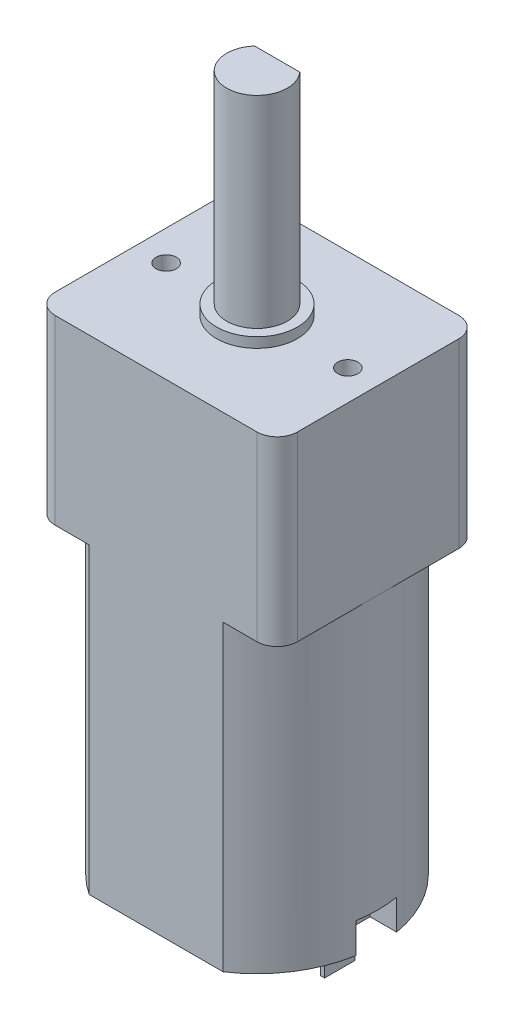
SolidWorks part; units mm, degrees
ref_plane "Front Plane" through (0, 0, 0) normal (0, 0, 1) x (1, 0, 0)
ref_plane "Top Plane" through (0, 0, 0) normal (0, 1, 0) x (1, 0, 0)
ref_plane "Right Plane" through (0, 0, 0) normal (1, 0, 0) x (0, 0, -1)
sketch "Sketch1" plane through (0, 0, 0) normal (0, 1, 0) x (1, 0, 0)
  line L0 (-3.3166, 5) -> (3.3166, 5)
  line L1 (-3.3166, -5) -> (3.3166, -5)
  arc A0 (-3.3166, 5) -> (-3.3166, -5) centre (0, 0) ccw
  arc A1 (3.3166, -5) -> (3.3166, 5) centre (0, 0) ccw
  dimension "D1" = 12
  dimension "D2" = 10
extrude "Boss-Extrude1" add sketch "Sketch1" along normal blind 15
sketch "Sketch2" plane through (0, 0, 0) normal (0, -1, 0) x (1, 0, 0)
  circle A0 centre (0, 0) radius 2.5
  dimension "D1" = 5
extrude "Boss-Extrude2" add sketch "Sketch2" along normal blind 1.2
sketch "Sketch3" plane through (0, 0, 0) normal (0, -1, 0) x (1, 0, 0)
  line L0 (0, 5) -> (0, -5) construction
  line L1 (-3.3166, 5) -> (3.3166, 5) construction
  line L2 (3.3166, -5) -> (-3.3166, -5) construction
  line L3 (4.1, -0.75) -> (3.9, -0.75)
  line L4 (-4.1, 0.75) -> (-3.9, 0.75)
  line L5 (-4.1, 0.75) -> (-4.1, -0.75)
  line L6 (-4.1, -0.75) -> (-3.9, -0.75)
  line L7 (-3.9, 0.75) -> (-3.9, -0.75)
  line L8 (3.9, 0.75) -> (3.9, -0.75)
  line L9 (4.1, 0.75) -> (3.9, 0.75)
  line L10 (4.1, 0.75) -> (4.1, -0.75)
  point P10 (-3.9, 0)
  point P15 (-4, -0.75)
  point P17 (4, -0.75)
  dimension "D1" = 1.5
  dimension "D2" = 0.2
  dimension "D3" = 8
extrude "Boss-Extrude3" add sketch "Sketch3" along normal blind 2
sketch "Sketch4" plane through (0, 0, 0) normal (0, -1, 0) x (1, 0, 0)
  line L0 (0, 5) -> (0, -5) construction
  line L1 (-6, 1) -> (-4.6, 1)
  line L2 (-6, 1) -> (-6, -1)
  line L3 (-6, -1) -> (-4.6, -1)
  line L4 (-4.6, 1) -> (-4.6, -1)
  line L5 (-3.3166, 5) -> (3.3166, 5) construction
  line L6 (3.3166, -5) -> (-3.3166, -5) construction
  line L7 (6, -1) -> (4.6, -1)
  line L8 (4.6, 1) -> (4.6, -1)
  line L9 (6, 1) -> (4.6, 1)
  line L10 (6, 1) -> (6, -1)
  arc A0 (-3.3166, 5) -> (-3.3166, -5) centre (0, 0) ccw construction
  point P13 (-6, 0)
  point P14 (-4.6, 0)
  dimension "D1" = 1.4
  dimension "D2" = 2
extrude "Cut-Extrude1" cut sketch "Sketch4" against normal blind 1.5
sketch "Sketch5" plane through (0, 15, 0) normal (0, 1, 0) x (1, 0, 0)
  line L0 (3.3166, 5) -> (-3.3166, 5) construction
  line L1 (-5, 5) -> (5, 5)
  line L2 (-6, 4) -> (-6, -4)
  line L3 (-5, -5) -> (5, -5)
  line L4 (6, 4) -> (6, -4)
  line L5 (-3.3166, -5) -> (3.3166, -5) construction
  arc A0 (3.3166, -5) -> (3.3166, 5) centre (0, 0) ccw construction
  arc A1 (-3.3166, 5) -> (-3.3166, -5) centre (0, 0) ccw construction
  arc A2 (5, 5) -> (6, 4) centre (5, 4) cw
  arc A3 (5, -5) -> (6, -4) centre (5, -4) ccw
  arc A4 (-6, -4) -> (-5, -5) centre (-5, -4) ccw
  arc A5 (-5, 5) -> (-6, 4) centre (-5, 4) ccw
  dimension "D1" = 1
extrude "Boss-Extrude4" add sketch "Sketch5" along normal blind 9
sketch "Sketch6" plane through (0, 24, 0) normal (0, 1, 0) x (1, 0, 0)
  line L0 (-1.118, 1) -> (1.118, 1)
  line L1 (-5, -5) -> (5, -5) construction
  arc A0 (-1.118, 1) -> (1.118, 1) centre (0, 0) ccw
  dimension "D1" = 3
  dimension "D2" = 1
extrude "Boss-Extrude5" add sketch "Sketch6" along normal blind 10.5
sketch "Sketch7" plane through (0, 24, 0) normal (0, 1, 0) x (1, 0, 0)
  circle A0 centre (0, 0) radius 2
  dimension "D1" = 4
extrude "Boss-Extrude6" add sketch "Sketch7" along normal blind 0.5
sketch "Sketch8" plane through (0, 24, 0) normal (0, 1, 0) x (1, 0, 0)
  line L0 (0, 5) -> (0, -5) construction
  line L1 (5, 5) -> (-5, 5) construction
  line L2 (-5, -5) -> (5, -5) construction
  circle A0 centre (-4.5, 0) radius 0.5
  circle A1 centre (4.5, 0) radius 0.5
  point P8 (0, 0)
  dimension "D1" = 1
  dimension "D2" = 9
extrude "Cut-Extrude2" cut sketch "Sketch8" against normal blind 4.5
